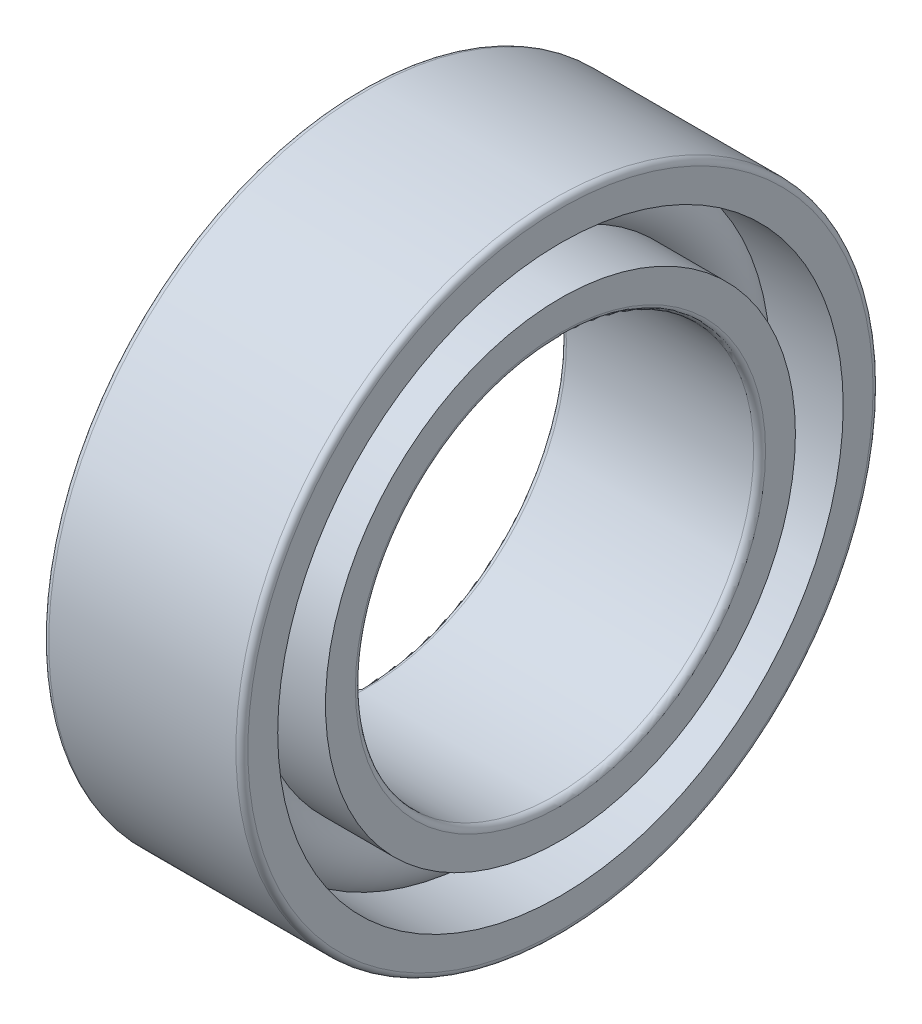
SolidWorks part; units mm, degrees
ref_plane "Plane1" through (0, 0, 0) normal (0, 0, 1) x (1, 0, 0)
ref_plane "Plane2" through (0, 0, 0) normal (0, 1, 0) x (1, 0, 0)
ref_plane "Plane3" through (0, 0, 0) normal (1, 0, 0) x (0, 0, -1)
sketch "Clipboard" plane through (0, 0, 0) normal (0, 0, 1) x (1, 0, 0)
  line L0 (-10, 0) -> (10, 0) construction
  line L1 (0, 0) -> (22.3471, -0.7804)
  line L2 (0, 0) -> (12.9921, 0.4537)
  line L3 (0, 0) -> (22.3471, -0.7804)
  line L4 (0, 0) -> (-22.3573, -0.3902)
  dimension "BallCLRad" = 13
  dimension "Count" = 2
  dimension "Show_count" = 2
  dimension "Max_count" = 2
  dimension "Min_count" = 1
sketch "CagSpiSke" plane through (0, 0, 0) normal (0, 0, 1) x (1, 0, 0)
  line L0 (0.18, 12.7) -> (0.18, 13.3)
  line L1 (0.18, 13.3) -> (-0.18, 13.3)
  line L2 (-0.18, 13.3) -> (-0.18, 12.7)
  line L3 (-0.18, 12.7) -> (0.18, 12.7)
  line L4 (-20.6375, 0) -> (20.6375, 0) construction
  line L5 (0, 0) -> (0, 23.7692) construction
  dimension "Thickness" = 0.36
  dimension "OD" = 26.6
  dimension "ID" = 25.4
revolve "CageSpine" add sketch "CagSpiSke" angle 0.001 about L4 reverse direction yes
ref_axis "Axis1" through (-50, 0, 0) along (1, 0, 0)
sketch "CagBalSke" plane through (0, 0, 0) normal (0, 0, 1) x (1, 0, 0)
  line L0 (-1.98, 13) -> (1.98, 13)
  line L1 (-1.905, 13) -> (1.905, 13) construction
  line L2 (-10, 0) -> (10, 0) construction
  line L3 (0, 0) -> (0, 24) construction
  arc A0 (1.98, 13) -> (-1.98, 13) centre (0, 13) cw
  dimension "CageWallOD" = 3.96
  dimension "BallCLRad" = 13
revolve "CageBall" [suppressed] add sketch "CagBalSke" angle 360 about L1 reverse direction yes
pattern_circular "CageBalls" [suppressed] count 2 every 180 about axis through (-50, 0, 0) along (1, 0, 0)
sketch "CagTrmODSke" plane through (0, 0, 0) normal (0, 0, 1) x (1, 0, 0)
  line L0 (1.981, 13.3) -> (1.981, 14.981)
  line L1 (1.981, 14.981) -> (-1.981, 14.981)
  line L2 (-1.981, 14.981) -> (-1.981, 13.3)
  line L3 (-1.981, 13.3) -> (1.981, 13.3)
  line L4 (-20.6375, 0) -> (20.6375, 0) construction
  line L5 (0, 0) -> (0, 25) construction
  dimension "Width" = 3.962
  dimension "ID" = 26.6
  dimension "OD" = 29.962
revolve "CageTrimOD" [suppressed] cut sketch "CagTrmODSke" angle 360 about L4 reverse direction yes
sketch "CagTrmIDSke" plane through (0, 0, 0) normal (0, 0, 1) x (1, 0, 0)
  line L0 (1.981, 11.021) -> (1.981, 12.7)
  line L1 (1.981, 12.7) -> (-1.981, 12.7)
  line L2 (-1.981, 12.7) -> (-1.981, 11.021)
  line L3 (-1.981, 11.021) -> (1.981, 11.021)
  line L4 (-20.6375, 0) -> (20.6375, 0) construction
  line L5 (0, 0) -> (0, 25) construction
  dimension "ID" = 22.042
  dimension "OD" = 25.4
  dimension "Width" = 3.962
revolve "CageTrimID" [suppressed] cut sketch "CagTrmIDSke" angle 360 about L4 reverse direction yes
sketch "BalSimSke" plane through (0, 0, 0) normal (0, 0, 1) x (1, 0, 0)
  line L0 (-10, 0) -> (10, 0) construction
  line L1 (-10, 13) -> (10, 13) construction
  line L2 (0, 0) -> (0, 23) construction
  circle A0 centre (0, 13) radius 1.8
  dimension "Ball_diameter" = 3.6
  dimension "BallCLRad" = 13
revolve "BallsSimplified" add sketch "BalSimSke" angle 360 about L0
sketch "BalDetSke" plane through (0, 0, 0) normal (0, 0, 1) x (1, 0, 0)
  line L0 (-1.8, 13) -> (1.8, 13)
  line L1 (-1.905, 13) -> (1.905, 13) construction
  line L2 (0, 0) -> (0, 25) construction
  arc A0 (1.8, 13) -> (-1.8, 13) centre (0, 13) cw
  dimension "Ball_diameter" = 3.6
  dimension "BallCLRad" = 13
revolve "BallDetailed" [suppressed] add sketch "BalDetSke" angle 360 about L1 reverse direction yes
sketch "InnRacSke" plane through (0, 0, 0) normal (0, 0, 1) x (1, 0, 0)
  line L0 (-1.3079, 11.8) -> (-5, 11.8)
  line L1 (-5, 11.8) -> (-5, 10.3)
  line L2 (-4.7, 10) -> (4.7, 10)
  line L3 (5, 10.3) -> (5, 11.8)
  line L4 (5, 11.8) -> (1.3079, 11.8)
  line L5 (-20.6375, 0) -> (20.6375, 0) construction
  line L6 (0, 0) -> (0, 30) construction
  arc A0 (-5, 10.3) -> (-4.7, 10) centre (-4.7, 10.3) ccw
  arc A1 (4.7, 10) -> (5, 10.3) centre (4.7, 10.3) ccw
  arc A2 (1.3079, 11.8) -> (-1.3079, 11.8) centre (0, 13) cw
  dimension "Fillet_radius" = 0.3
  dimension "Ball_diameter" = 3.55
  dimension "ID" = 20
  dimension "OD" = 23.6
  dimension "Width" = 10
  dimension "BallCLRad" = 13
revolve "InnerRace" add sketch "InnRacSke" angle 360 about L5 reverse direction yes
sketch "OutRacSke" plane through (0, 0, 0) normal (0, 0, 1) x (1, 0, 0)
  line L0 (-1.3079, 14.2) -> (-5, 14.2)
  line L1 (-5, 14.2) -> (-5, 15.7)
  line L2 (-4.7, 16) -> (4.7, 16)
  line L3 (5, 15.7) -> (5, 14.2)
  line L4 (5, 14.2) -> (1.3079, 14.2)
  line L5 (-20.6375, 0) -> (20.6375, 0) construction
  line L6 (0, 0) -> (0, 30) construction
  arc A0 (-5, 15.7) -> (-4.7, 16) centre (-4.7, 15.7) cw
  arc A1 (4.7, 16) -> (5, 15.7) centre (4.7, 15.7) cw
  arc A2 (1.3079, 14.2) -> (-1.3079, 14.2) centre (0, 13) ccw
  dimension "Fillet_radius" = 0.3
  dimension "Ball_diameter" = 3.55
  dimension "OD" = 32
  dimension "ID" = 28.4
  dimension "Width" = 10
  dimension "BallCLRad" = 13
revolve "OuterRace" add sketch "OutRacSke" angle 360 about L5 reverse direction yes
pattern_circular "BallsDetailed" [suppressed] count 2 every 180 about axis through (-50, 0, 0) along (1, 0, 0)
equation "\"BallCLRad@Clipboard\" = ( \"OD@OutRacSke\" + \"ID@InnRacSke\" ) / 4"
equation "\"BallCLRad@BalSimSke\" = \"BallCLRad@Clipboard\""
equation "\"BallCLRad@BalDetSke\" = \"BallCLRad@Clipboard\""
equation "\"BallCLRad@InnRacSke\" = \"BallCLRad@Clipboard\""
equation "\"BallCLRad@OutRacSke\" = \"BallCLRad@Clipboard\""
equation "\"Ball_diameter@InnRacSke\" = \"Ball_diameter@BalDetSke\" - 0.05"
equation "\"Ball_diameter@OutRacSke\" = \"Ball_diameter@BalDetSke\" - 0.05"
equation "\"Ball_diameter@BalSimSke\" = \"Ball_diameter@BalDetSke\""
equation "\"Width@OutRacSke\" = \"Width@InnRacSke\""
equation "\"Fillet_radius@OutRacSke\" = \"Fillet_radius@InnRacSke\""
equation "\"Max_count@Clipboard\" = int( 3.14159265 / atn(( \"Ball_diameter@BalDetSke\" / 2) / sqr( \"BallCLRad@Clipboard\"  *  \"BallCLRad@Clipboard\" - ( \"Ball_diameter@BalDetSke\" / 2) *  ( \"Ball_diameter@BalDetSke\" / 2))))"
equation "\"Max_count@Clipboard\" = ((sgn( \"Max_count@Clipboard\" - \"Count@Clipboard\" )-1)*( \"Max_count@Clipboard\" - \"Count@Clipboard\" ))/-2+ \"Count@Clipboard\""
equation "\"Count@BallsDetailed\" = int( \"Show_count@Clipboard\" ) "
equation "\"Count@BallsDetailed\" = ((sgn( \"Count@BallsDetailed\" - \"Max_count@Clipboard\" )-1)*( \"Count@BallsDetailed\" - \"Max_count@Clipboard\" ))/-2+ \"Max_count@Clipboard\""
equation "\"Count@BallsDetailed\" = ((sgn( \"Count@BallsDetailed\" - \"Min_count@Clipboard\" )+1)*( \"Count@BallsDetailed\" - \"Min_count@Clipboard\"))/2 +\"Min_count@Clipboard\""
equation "\"Angle@BallsDetailed\" = 360.0 / \"Max_count@Clipboard\""
equation "\"BallCLRad@CagBalSke\" = \"BallCLRad@Clipboard\""
equation "\"Count@CageBalls\" = \"Count@BallsDetailed\""
equation "\"Angle@CageBalls\" = \"Angle@BallsDetailed\""
equation "\"Angle@CageSpine\" =  \"Angle@CageBalls\" * ( \"Count@CageBalls\" -1 + int( \"Count@CageBalls\" / \"Max_count@Clipboard\" ) )  + 0.001 -  int( \"Count@CageBalls\" / \"Max_count@Clipboard\" ) * 0.001"
equation "\"Angle@CageSpine\" =  \"Angle@CageSpine\" * int( \"Min_count@Clipboard\" / 2) + int(1 / \"Min_count@Clipboard\")  * 0.001"
equation "\"CageWallOD@CagBalSke\" =  \"Ball_diameter@BalDetSke\" * 1.1"
equation "\"Thickness@CagSpiSke\" =  \"Ball_diameter@BalDetSke\" * 0.1"
equation "\"OD@CagTrmODSke\" = \"BallCLRad@Clipboard\" * 2 + \"CageWallOD@CagBalSke\" + 0.002"
equation "\"ID@CagTrmODSke\" = \"BallCLRad@Clipboard\" * 2 + \"Ball_diameter@BalDetSke\" / 6"
equation "\"OD@CagTrmIDSke\" = \"BallCLRad@Clipboard\" * 2 - \"Ball_diameter@BalDetSke\" / 6"
equation "\"ID@CagTrmIDSke\" = \"BallCLRad@Clipboard\" * 2 - \"CageWallOD@CagBalSke\" + 0.002"
equation "\"OD@CagSpiSke\" = \"ID@CagTrmODSke\""
equation "\"ID@CagSpiSke\" = \"OD@CagTrmIDSke\""
equation "\"Width@CagTrmODSke\" = \"CageWallOD@CagBalSke\" + 0.002"
equation "\"Width@CagTrmIDSke\" = \"CageWallOD@CagBalSke\" + 0.002"
